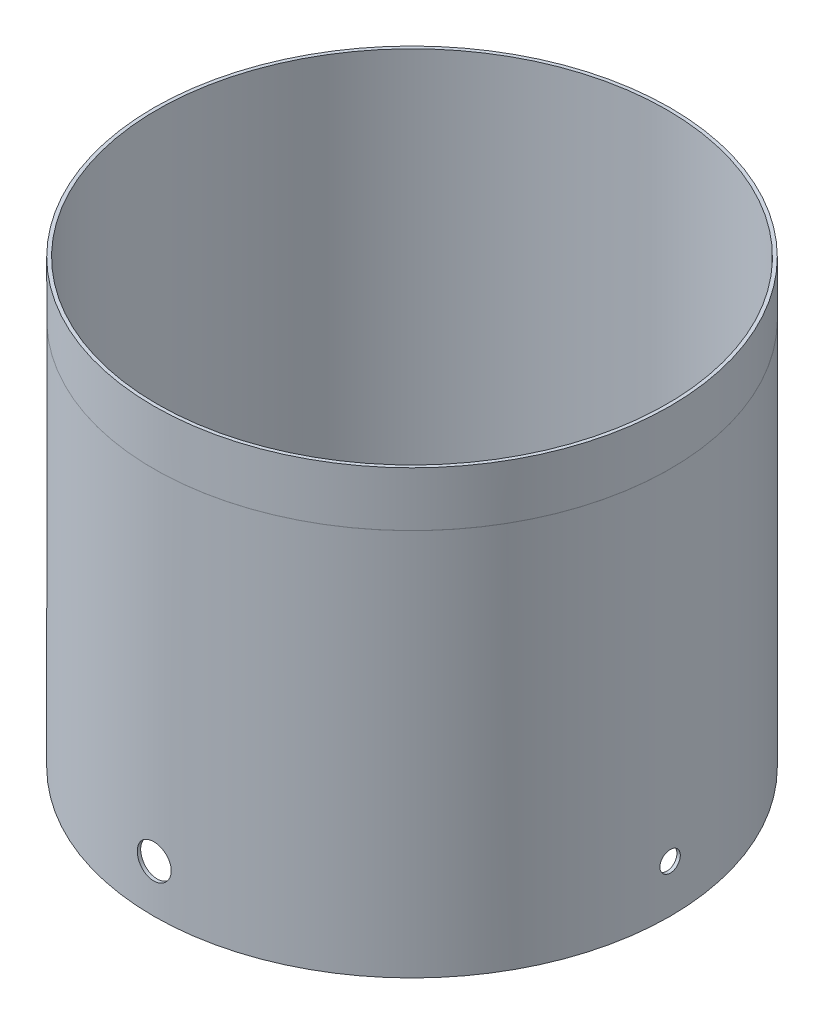
SolidWorks part; units mm, degrees
material "Stainless Steel (ferritic)"
ref_plane "Front Plane" through (0, 0, 0) normal (0, 0, 1) x (1, 0, 0)
ref_plane "Top Plane" through (0, 0, 0) normal (0, 1, 0) x (1, 0, 0)
ref_plane "Right Plane" through (0, 0, 0) normal (1, 0, 0) x (0, 0, -1)
sketch "Sketch1" plane through (0, 0, 0) normal (0, 1, 0) x (1, 0, 0)
  circle A0 centre (0, 0) radius 37.5
  circle A1 centre (0, 0) radius 38
  dimension "D2" = 75
  dimension "D1" = 0.5
extrude "Boss-Extrude1" add sketch "Sketch1" along normal blind 65
sketch "Sketch2" plane through (0, 0, 0) normal (1, 0, 0) x (0, 0, -1)
  line L5 (-38, 0) -> (38, 0) construction
  circle A0 centre (0, 7) radius 1.5
  dimension "D1" = 3
  dimension "D2" = 5.5
extrude "Cut-Extrude1" cut sketch "Sketch2" against normal through all both and the other way through all
sketch "Sketch4" plane through (0, 0, 0) normal (0, 0, 1) x (1, 0, 0)
  line L1 (-38, 0) -> (38, 0) construction
  circle A0 centre (0, 7) radius 2.5
  dimension "D1" = 5
  dimension "D2" = 4.5
extrude "Cut-Extrude2" cut sketch "Sketch4" against normal through all both and the other way through all
ref_plane "Plane2" through (0, 0, 38) normal (0, 0, 1) x (1, 0, 0)
sketch "Sketch6" plane through (0, 0, 38) normal (0, 0, 1) x (1, 0, 0)
  line L0 (0, 65) -> (0, 9.5) construction
  line L1 (38, 65) -> (-38, 65) construction
  line L2 (0, 4.5) -> (0, 0) construction
  circle A0 centre (0, 7) radius 2.5 construction
ref_plane "Plane3" through (38, 0, 0) normal (1, 0, 0) x (0, 0, -1)
sketch "Sketch7" plane through (38, 0, 0) normal (1, 0, 0) x (0, 0, -1)
  line L0 (0, 5.5) -> (0, 0) construction
  line L1 (0, 65) -> (0, 8.5) construction
  line L2 (38, 65) -> (-38, 65) construction
  circle A0 centre (0, 7) radius 1.5 construction
ref_plane "Plane4" through (0, 0, -46.7396) normal (0, 0, 1) x (1, 0, 0)
sketch "Sketch8" plane through (0, 0, -46.7396) normal (0, 0, 1) x (1, 0, 0)
  line L0 (37.5, 65) -> (-37.5, 65) construction
  line L1 (119.3805, 57) -> (-119.3805, 57)
  line L2 (119.3805, 57) -> (119.3805, 56.99)
  line L3 (119.3805, 56.99) -> (-119.3805, 56.99)
  line L4 (-119.3805, 57) -> (-119.3805, 56.99)
  point P4 (0, 56.99)
  dimension "D1" = 238.761
  dimension "D2" = 8
  dimension "D3" = 0.01
wrap "Wrap1" sketch "Sketch8" wrap type scribe source sketch "Sketch8" face at (0.5689, 4.5656, -37.9957)
equation "\"D1@Sketch8\"=pi*76"
